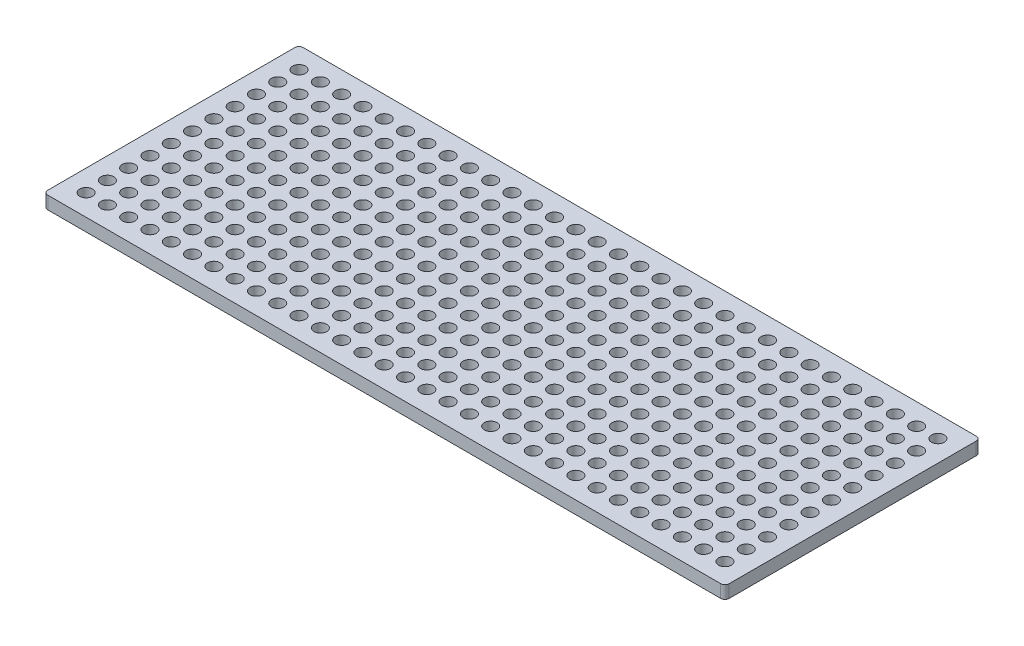
SolidWorks part; units mm, degrees
ref_plane "Front Plane" through (0, 0, 0) normal (0, 0, 1) x (1, 0, 0)
ref_plane "Top Plane" through (0, 0, 0) normal (0, 1, 0) x (1, 0, 0)
ref_plane "Right Plane" through (0, 0, 0) normal (1, 0, 0) x (0, 0, -1)
sketch "Sketch1" plane through (0, 0, 0) normal (0, 1, 0) x (1, 0, 0)
  line L1 (-80, -30) -> (80, -30)
  line L2 (-80, -30) -> (-80, 30)
  line L3 (-80, 30) -> (80, 30)
  line L4 (80, -30) -> (80, 30)
  line L5 (-80, -30) -> (80, 30) construction
  line L6 (-80, 30) -> (80, -30) construction
  circle A0 centre (-75, 25) radius 1.5
  circle A1 centre (-70, 25) radius 1.5
  circle A2 centre (-65, 25) radius 1.5
  circle A3 centre (-60, 25) radius 1.5
  circle A4 centre (-55, 25) radius 1.5
  circle A5 centre (-50, 25) radius 1.5
  circle A6 centre (-45, 25) radius 1.5
  circle A7 centre (-40, 25) radius 1.5
  circle A8 centre (-35, 25) radius 1.5
  circle A9 centre (-30, 25) radius 1.5
  circle A10 centre (-25, 25) radius 1.5
  circle A11 centre (-20, 25) radius 1.5
  circle A12 centre (-15, 25) radius 1.5
  circle A13 centre (-10, 25) radius 1.5
  circle A14 centre (-5, 25) radius 1.5
  circle A15 centre (0, 25) radius 1.5
  circle A16 centre (5, 25) radius 1.5
  circle A17 centre (10, 25) radius 1.5
  circle A18 centre (15, 25) radius 1.5
  circle A19 centre (20, 25) radius 1.5
  circle A20 centre (25, 25) radius 1.5
  circle A21 centre (30, 25) radius 1.5
  circle A22 centre (35, 25) radius 1.5
  circle A23 centre (40, 25) radius 1.5
  circle A24 centre (45, 25) radius 1.5
  circle A25 centre (50, 25) radius 1.5
  circle A26 centre (55, 25) radius 1.5
  circle A27 centre (60, 25) radius 1.5
  circle A28 centre (65, 25) radius 1.5
  circle A29 centre (70, 25) radius 1.5
  circle A30 centre (75, 25) radius 1.5
  circle A31 centre (-75, 20) radius 1.5
  circle A32 centre (-75, 15) radius 1.5
  circle A33 centre (-75, 10) radius 1.5
  circle A34 centre (-75, 5) radius 1.5
  circle A35 centre (-75, 0) radius 1.5
  circle A36 centre (-75, -5) radius 1.5
  circle A37 centre (-75, -10) radius 1.5
  circle A38 centre (-75, -15) radius 1.5
  circle A39 centre (-75, -20) radius 1.5
  circle A40 centre (-75, -25) radius 1.5
  circle A41 centre (-70, 20) radius 1.5
  circle A42 centre (-70, 10) radius 1.5
  circle A43 centre (-70, 5) radius 1.5
  circle A44 centre (-70, 0) radius 1.5
  circle A45 centre (-70, -5) radius 1.5
  circle A46 centre (-70, -10) radius 1.5
  circle A47 centre (-70, -15) radius 1.5
  circle A48 centre (-70, -20) radius 1.5
  circle A49 centre (-70, -25) radius 1.5
  circle A50 centre (-65, 20) radius 1.5
  circle A51 centre (-65, 10) radius 1.5
  circle A52 centre (-65, 5) radius 1.5
  circle A53 centre (-65, 0) radius 1.5
  circle A54 centre (-65, -5) radius 1.5
  circle A55 centre (-65, -10) radius 1.5
  circle A56 centre (-65, -15) radius 1.5
  circle A57 centre (-65, -20) radius 1.5
  circle A58 centre (-65, -25) radius 1.5
  circle A59 centre (-60, 20) radius 1.5
  circle A60 centre (-60, 10) radius 1.5
  circle A61 centre (-60, 5) radius 1.5
  circle A62 centre (-60, 0) radius 1.5
  circle A63 centre (-60, -5) radius 1.5
  circle A64 centre (-60, -10) radius 1.5
  circle A65 centre (-60, -15) radius 1.5
  circle A66 centre (-60, -20) radius 1.5
  circle A67 centre (-60, -25) radius 1.5
  circle A68 centre (-55, 20) radius 1.5
  circle A69 centre (-55, 10) radius 1.5
  circle A70 centre (-55, 5) radius 1.5
  circle A71 centre (-55, 0) radius 1.5
  circle A72 centre (-55, -5) radius 1.5
  circle A73 centre (-55, -10) radius 1.5
  circle A74 centre (-55, -15) radius 1.5
  circle A75 centre (-55, -20) radius 1.5
  circle A76 centre (-55, -25) radius 1.5
  circle A77 centre (-50, 20) radius 1.5
  circle A78 centre (-50, 10) radius 1.5
  circle A79 centre (-50, 5) radius 1.5
  circle A80 centre (-50, 0) radius 1.5
  circle A81 centre (-50, -5) radius 1.5
  circle A82 centre (-50, -10) radius 1.5
  circle A83 centre (-50, -15) radius 1.5
  circle A84 centre (-50, -20) radius 1.5
  circle A85 centre (-50, -25) radius 1.5
  circle A86 centre (-45, 20) radius 1.5
  circle A87 centre (-45, 10) radius 1.5
  circle A88 centre (-45, 5) radius 1.5
  circle A89 centre (-45, 0) radius 1.5
  circle A90 centre (-45, -5) radius 1.5
  circle A91 centre (-45, -10) radius 1.5
  circle A92 centre (-45, -15) radius 1.5
  circle A93 centre (-45, -20) radius 1.5
  circle A94 centre (-45, -25) radius 1.5
  circle A95 centre (-40, 20) radius 1.5
  circle A96 centre (-40, 10) radius 1.5
  circle A97 centre (-40, 5) radius 1.5
  circle A98 centre (-40, 0) radius 1.5
  circle A99 centre (-40, -5) radius 1.5
  circle A100 centre (-40, -10) radius 1.5
  circle A101 centre (-40, -15) radius 1.5
  circle A102 centre (-40, -20) radius 1.5
  circle A103 centre (-40, -25) radius 1.5
  circle A104 centre (-35, 20) radius 1.5
  circle A105 centre (-35, 10) radius 1.5
  circle A106 centre (-35, 5) radius 1.5
  circle A107 centre (-35, 0) radius 1.5
  circle A108 centre (-35, -5) radius 1.5
  circle A109 centre (-35, -10) radius 1.5
  circle A110 centre (-35, -15) radius 1.5
  circle A111 centre (-35, -20) radius 1.5
  circle A112 centre (-35, -25) radius 1.5
  circle A113 centre (-30, 20) radius 1.5
  circle A114 centre (-30, 10) radius 1.5
  circle A115 centre (-30, 5) radius 1.5
  circle A116 centre (-30, 0) radius 1.5
  circle A117 centre (-30, -5) radius 1.5
  circle A118 centre (-30, -10) radius 1.5
  circle A119 centre (-30, -15) radius 1.5
  circle A120 centre (-30, -20) radius 1.5
  circle A121 centre (-30, -25) radius 1.5
  circle A122 centre (-25, 20) radius 1.5
  circle A123 centre (-25, 10) radius 1.5
  circle A124 centre (-25, 5) radius 1.5
  circle A125 centre (-25, 0) radius 1.5
  circle A126 centre (-25, -5) radius 1.5
  circle A127 centre (-25, -10) radius 1.5
  circle A128 centre (-25, -15) radius 1.5
  circle A129 centre (-25, -20) radius 1.5
  circle A130 centre (-25, -25) radius 1.5
  circle A131 centre (-20, 20) radius 1.5
  circle A132 centre (-20, 10) radius 1.5
  circle A133 centre (-20, 5) radius 1.5
  circle A134 centre (-20, 0) radius 1.5
  circle A135 centre (-20, -5) radius 1.5
  circle A136 centre (-20, -10) radius 1.5
  circle A137 centre (-20, -15) radius 1.5
  circle A138 centre (-20, -20) radius 1.5
  circle A139 centre (-20, -25) radius 1.5
  circle A140 centre (-15, 20) radius 1.5
  circle A141 centre (-15, 10) radius 1.5
  circle A142 centre (-15, 5) radius 1.5
  circle A143 centre (-15, 0) radius 1.5
  circle A144 centre (-15, -5) radius 1.5
  circle A145 centre (-15, -10) radius 1.5
  circle A146 centre (-15, -15) radius 1.5
  circle A147 centre (-15, -20) radius 1.5
  circle A148 centre (-15, -25) radius 1.5
  circle A149 centre (-10, 20) radius 1.5
  circle A150 centre (-10, 10) radius 1.5
  circle A151 centre (-10, 5) radius 1.5
  circle A152 centre (-10, 0) radius 1.5
  circle A153 centre (-10, -5) radius 1.5
  circle A154 centre (-10, -10) radius 1.5
  circle A155 centre (-10, -15) radius 1.5
  circle A156 centre (-10, -20) radius 1.5
  circle A157 centre (-10, -25) radius 1.5
  circle A158 centre (-5, 20) radius 1.5
  circle A159 centre (-5, 10) radius 1.5
  circle A160 centre (-5, 5) radius 1.5
  circle A161 centre (-5, 0) radius 1.5
  circle A162 centre (-5, -5) radius 1.5
  circle A163 centre (-5, -10) radius 1.5
  circle A164 centre (-5, -15) radius 1.5
  circle A165 centre (-5, -20) radius 1.5
  circle A166 centre (-5, -25) radius 1.5
  circle A167 centre (0, 20) radius 1.5
  circle A168 centre (0, 10) radius 1.5
  circle A169 centre (0, 5) radius 1.5
  circle A170 centre (0, 0) radius 1.5
  circle A171 centre (0, -5) radius 1.5
  circle A172 centre (0, -10) radius 1.5
  circle A173 centre (0, -15) radius 1.5
  circle A174 centre (0, -20) radius 1.5
  circle A175 centre (0, -25) radius 1.5
  circle A176 centre (5, 20) radius 1.5
  circle A177 centre (5, 10) radius 1.5
  circle A178 centre (5, 5) radius 1.5
  circle A179 centre (5, 0) radius 1.5
  circle A180 centre (5, -5) radius 1.5
  circle A181 centre (5, -10) radius 1.5
  circle A182 centre (5, -15) radius 1.5
  circle A183 centre (5, -20) radius 1.5
  circle A184 centre (5, -25) radius 1.5
  circle A185 centre (10, 20) radius 1.5
  circle A186 centre (10, 10) radius 1.5
  circle A187 centre (10, 5) radius 1.5
  circle A188 centre (10, 0) radius 1.5
  circle A189 centre (10, -5) radius 1.5
  circle A190 centre (10, -10) radius 1.5
  circle A191 centre (10, -15) radius 1.5
  circle A192 centre (10, -20) radius 1.5
  circle A193 centre (10, -25) radius 1.5
  circle A194 centre (15, 20) radius 1.5
  circle A195 centre (15, 10) radius 1.5
  circle A196 centre (15, 5) radius 1.5
  circle A197 centre (15, 0) radius 1.5
  circle A198 centre (15, -5) radius 1.5
  circle A199 centre (15, -10) radius 1.5
  circle A200 centre (15, -15) radius 1.5
  circle A201 centre (15, -20) radius 1.5
  circle A202 centre (15, -25) radius 1.5
  circle A203 centre (20, 20) radius 1.5
  circle A204 centre (20, 10) radius 1.5
  circle A205 centre (20, 5) radius 1.5
  circle A206 centre (20, 0) radius 1.5
  circle A207 centre (20, -5) radius 1.5
  circle A208 centre (20, -10) radius 1.5
  circle A209 centre (20, -15) radius 1.5
  circle A210 centre (20, -20) radius 1.5
  circle A211 centre (20, -25) radius 1.5
  circle A212 centre (25, 20) radius 1.5
  circle A213 centre (25, 10) radius 1.5
  circle A214 centre (25, 5) radius 1.5
  circle A215 centre (25, 0) radius 1.5
  circle A216 centre (25, -5) radius 1.5
  circle A217 centre (25, -10) radius 1.5
  circle A218 centre (25, -15) radius 1.5
  circle A219 centre (25, -20) radius 1.5
  circle A220 centre (25, -25) radius 1.5
  circle A221 centre (30, 20) radius 1.5
  circle A222 centre (30, 10) radius 1.5
  circle A223 centre (30, 5) radius 1.5
  circle A224 centre (30, 0) radius 1.5
  circle A225 centre (30, -5) radius 1.5
  circle A226 centre (30, -10) radius 1.5
  circle A227 centre (30, -15) radius 1.5
  circle A228 centre (30, -20) radius 1.5
  circle A229 centre (30, -25) radius 1.5
  circle A230 centre (35, 20) radius 1.5
  circle A231 centre (35, 10) radius 1.5
  circle A232 centre (35, 5) radius 1.5
  circle A233 centre (35, 0) radius 1.5
  circle A234 centre (35, -5) radius 1.5
  circle A235 centre (35, -10) radius 1.5
  circle A236 centre (35, -15) radius 1.5
  circle A237 centre (35, -20) radius 1.5
  circle A238 centre (35, -25) radius 1.5
  circle A239 centre (40, 20) radius 1.5
  circle A240 centre (40, 10) radius 1.5
  circle A241 centre (40, 5) radius 1.5
  circle A242 centre (40, 0) radius 1.5
  circle A243 centre (40, -5) radius 1.5
  circle A244 centre (40, -10) radius 1.5
  circle A245 centre (40, -15) radius 1.5
  circle A246 centre (40, -20) radius 1.5
  circle A247 centre (40, -25) radius 1.5
  circle A248 centre (45, 20) radius 1.5
  circle A249 centre (45, 10) radius 1.5
  circle A250 centre (45, 5) radius 1.5
  circle A251 centre (45, 0) radius 1.5
  circle A252 centre (45, -5) radius 1.5
  circle A253 centre (45, -10) radius 1.5
  circle A254 centre (45, -15) radius 1.5
  circle A255 centre (45, -20) radius 1.5
  circle A256 centre (45, -25) radius 1.5
  circle A257 centre (50, 20) radius 1.5
  circle A258 centre (50, 10) radius 1.5
  circle A259 centre (50, 5) radius 1.5
  circle A260 centre (50, 0) radius 1.5
  circle A261 centre (50, -5) radius 1.5
  circle A262 centre (50, -10) radius 1.5
  circle A263 centre (50, -15) radius 1.5
  circle A264 centre (50, -20) radius 1.5
  circle A265 centre (50, -25) radius 1.5
  circle A266 centre (55, 20) radius 1.5
  circle A267 centre (55, 10) radius 1.5
  circle A268 centre (55, 5) radius 1.5
  circle A269 centre (55, 0) radius 1.5
  circle A270 centre (55, -5) radius 1.5
  circle A271 centre (55, -10) radius 1.5
  circle A272 centre (55, -15) radius 1.5
  circle A273 centre (55, -20) radius 1.5
  circle A274 centre (55, -25) radius 1.5
  circle A275 centre (60, 20) radius 1.5
  circle A276 centre (60, 10) radius 1.5
  circle A277 centre (60, 5) radius 1.5
  circle A278 centre (60, 0) radius 1.5
  circle A279 centre (60, -5) radius 1.5
  circle A280 centre (60, -10) radius 1.5
  circle A281 centre (60, -15) radius 1.5
  circle A282 centre (60, -20) radius 1.5
  circle A283 centre (60, -25) radius 1.5
  circle A284 centre (65, 20) radius 1.5
  circle A285 centre (65, 10) radius 1.5
  circle A286 centre (65, 5) radius 1.5
  circle A287 centre (65, 0) radius 1.5
  circle A288 centre (65, -5) radius 1.5
  circle A289 centre (65, -10) radius 1.5
  circle A290 centre (65, -15) radius 1.5
  circle A291 centre (65, -20) radius 1.5
  circle A292 centre (65, -25) radius 1.5
  circle A293 centre (70, 20) radius 1.5
  circle A294 centre (70, 10) radius 1.5
  circle A295 centre (70, 5) radius 1.5
  circle A296 centre (70, 0) radius 1.5
  circle A297 centre (70, -5) radius 1.5
  circle A298 centre (70, -10) radius 1.5
  circle A299 centre (70, -15) radius 1.5
  circle A300 centre (70, -20) radius 1.5
  circle A301 centre (70, -25) radius 1.5
  circle A302 centre (75, 20) radius 1.5
  circle A303 centre (75, 10) radius 1.5
  circle A304 centre (75, 5) radius 1.5
  circle A305 centre (75, 0) radius 1.5
  circle A306 centre (75, -5) radius 1.5
  circle A307 centre (75, -10) radius 1.5
  circle A308 centre (75, -15) radius 1.5
  circle A309 centre (75, -20) radius 1.5
  circle A310 centre (75, -25) radius 1.5
  circle A311 centre (-70, 15) radius 1.5
  circle A312 centre (-65, 15) radius 1.5
  circle A313 centre (-60, 15) radius 1.5
  circle A314 centre (-55, 15) radius 1.5
  circle A315 centre (-50, 15) radius 1.5
  circle A316 centre (-45, 15) radius 1.5
  circle A317 centre (-40, 15) radius 1.5
  circle A318 centre (-35, 15) radius 1.5
  circle A319 centre (-30, 15) radius 1.5
  circle A320 centre (-25, 15) radius 1.5
  circle A321 centre (-20, 15) radius 1.5
  circle A322 centre (-15, 15) radius 1.5
  circle A323 centre (-10, 15) radius 1.5
  circle A324 centre (-5, 15) radius 1.5
  circle A325 centre (0, 15) radius 1.5
  circle A326 centre (5, 15) radius 1.5
  circle A327 centre (10, 15) radius 1.5
  circle A328 centre (15, 15) radius 1.5
  circle A329 centre (20, 15) radius 1.5
  circle A330 centre (25, 15) radius 1.5
  circle A331 centre (30, 15) radius 1.5
  circle A332 centre (35, 15) radius 1.5
  circle A333 centre (40, 15) radius 1.5
  circle A334 centre (45, 15) radius 1.5
  circle A335 centre (50, 15) radius 1.5
  circle A336 centre (55, 15) radius 1.5
  circle A337 centre (60, 15) radius 1.5
  circle A338 centre (65, 15) radius 1.5
  circle A339 centre (70, 15) radius 1.5
  circle A340 centre (75, 15) radius 1.5
  point P0 (0, 0)
  dimension "D3" = 3
  dimension "D1" = 160
  dimension "D2" = 60
  dimension "D4" = 5
  dimension "D5" = 5
  dimension "D6" = 31
  dimension "D7" = 11
  dimension "D8" = 31
  dimension "D9" = 31
extrude "Boss-Extrude1" add sketch "Sketch1" along normal blind 3
fillet "Fillet2" radius 1 1 edges at (-80, 1.5, 30)
fillet "Fillet3" radius 1 1 edges at (-80, 1.5, -30)
fillet "Fillet4" radius 1 1 edges at (80, 1.5, 30)
fillet "Fillet5" radius 1 1 edges at (80, 1.5, -30)
